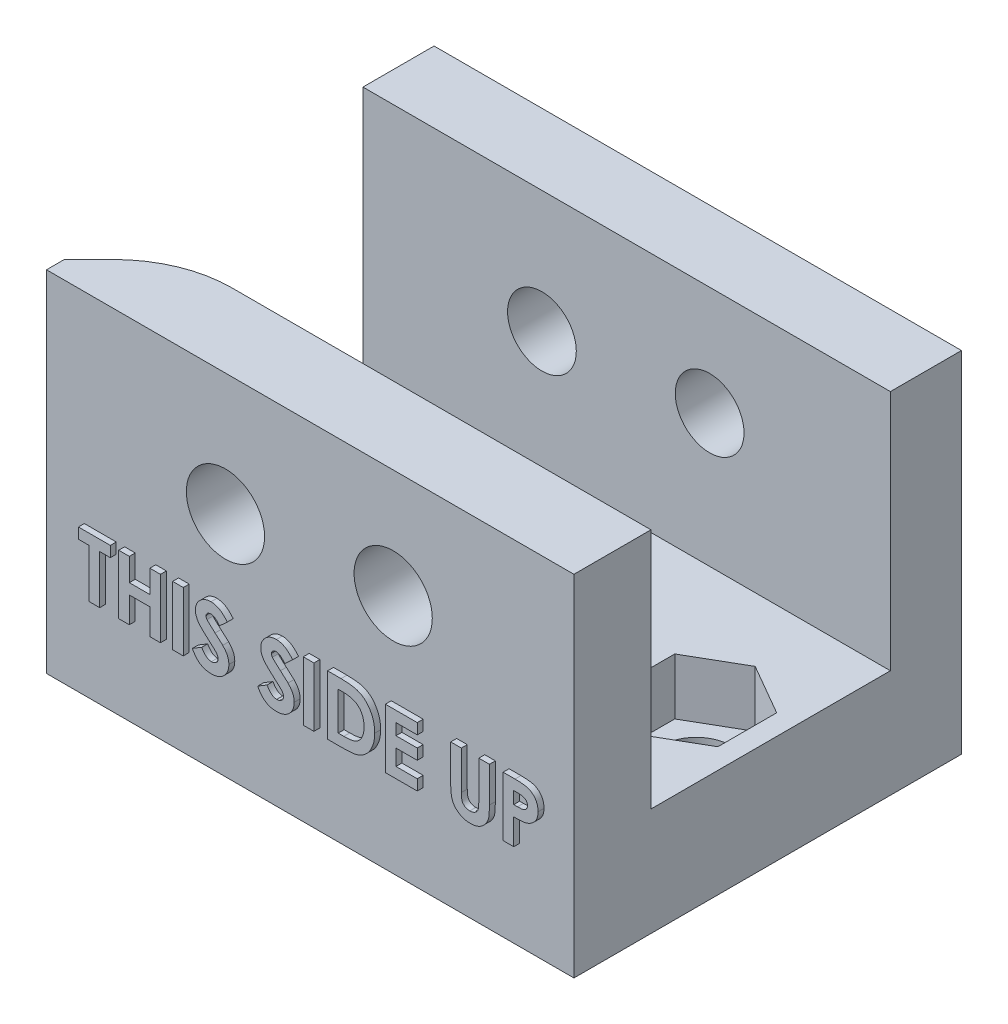
SolidWorks part; units mm, degrees
note: The reader was unsure of these and kept them because the rebuilt part matched: shared geometry of "Sketch2<3>".
material "PETG"
ref_plane "Płaszczyzna przednia" through (0, 0, 0) normal (0, 0, 1) x (1, 0, 0)
ref_plane "Płaszczyzna górna" through (0, 0, 0) normal (0, 1, 0) x (1, 0, 0)
ref_plane "Płaszczyzna prawa" through (0, 0, 0) normal (1, 0, 0) x (0, 0, -1)
sketch "Sketch1" plane through (0, 0, 0) normal (0, 0, 1) x (1, 0, 0)
  line L3 (-14.75, 10) -> (29.75, 10)
  line L4 (-14.75, 10) -> (-14.75, -10)
  line L5 (-14.75, -10) -> (29.75, -10)
  line L6 (29.75, 10) -> (29.75, -10)
  dimension "D5" = 20
extrude "Boss-Extrude1" add sketch "Sketch1" along normal blind 6
sketch "Sketch2" plane through (0, 0, 6) normal (0, 0, 1) x (1, 0, 0)
  line L0 (29.75, -10) -> (29.75, 10) construction
  line L1 (-14.75, -10) -> (29.75, -10)
  line L2 (-14.75, -10) -> (-14.75, -19.5)
  line L3 (-14.75, -19.5) -> (29.75, -19.5)
  line L4 (29.75, -10) -> (29.75, -19.5)
  line L6 (-14.75, -19.5) -> (29.75, -19.5)
  line L7 (-14.75, -19.5) -> (-14.75, -10.4)
  line L8 (-14.75, -10.4) -> (29.75, -10.4)
  line L9 (29.75, -19.5) -> (29.75, -10.4)
  dimension "D1" = 9.5
  dimension "D2" = 9.1
extrude "Boss-Extrude2" add sketch "Sketch2" against normal blind 6
extrude "Boss-Extrude3" add sketch "Sketch2<3>" along normal blind 20.2 contours L8 L2 L3 L4
sketch "Sketch2<3>" plane through (0, 0, 6) normal (0, 0, 1) x (1, 0, 0) same geometry as "Sketch2"
sketch "Sketch3" plane through (0, 0, 26.2) normal (0, 0, 1) x (1, 0, 0)
  line L4 (-14.75, 10) -> (-14.75, -10.4)
  line L5 (-14.75, -10.4) -> (29.75, -10.4)
  line L6 (29.75, -10.4) -> (29.75, 10)
  line L7 (29.75, 10) -> (-14.75, 10)
  line L8 (-14.75, 10) -> (-14.75, -10.4)
  line L10 (29.75, -10.4) -> (29.75, 10)
  line L11 (29.75, 10) -> (-14.75, 10)
  line L12 (29.75, -10.4) -> (-14.75, -10.4)
  line L13 (-14.75, -10.4) -> (-14.75, -19.5)
  line L14 (-14.75, -19.5) -> (29.75, -19.5)
  line L15 (29.75, -19.5) -> (29.75, -10.4)
  line L17 (-14.75, -10.4) -> (-14.75, -19.5)
  line L18 (-14.75, -19.5) -> (29.75, -19.5)
  line L19 (29.75, -19.5) -> (29.75, -10.4)
  dimension "D1" = 0
  dimension "D2" = 0
extrude "Boss-Extrude4" add sketch "Sketch3" along normal blind 6.5
sketch "Sketch4" plane through (0, -19.5, 0) normal (0, -1, 0) x (1, 0, 0)
  line L0 (-14.75, 0) -> (29.75, 0) construction
  line L1 (-2.7, 0) -> (17.7, 0) construction
  line L2 (-2.7, 0) -> (-2.7, 32.7) construction
  line L3 (-2.7, 32.7) -> (17.7, 32.7) construction
  line L4 (17.7, 0) -> (17.7, 32.7) construction
  line L5 (-14.75, 32.7) -> (29.75, 32.7) construction
  line L6 (-2.7, 32.7) -> (-14.75, 32.7) construction
  line L7 (-8.725, 32.7) -> (-8.725, 16.35) construction
  line L8 (-14.75, 0) -> (-14.75, 32.7) construction
  line L9 (-8.725, 16.35) -> (-14.75, 16.35) construction
  line L10 (7.5, 32.7) -> (7.5, 0) construction
  circle A0 centre (-8.725, 16.35) radius 2.9
  circle A1 centre (23.725, 16.35) radius 2.9
  point P8 (7.5, 32.7)
  point P9 (7.5, 32.7)
  dimension "D2" = 5.8
  dimension "D1" = 20.4
extrude "Cut-Extrude1" cut sketch "Sketch4" against normal through all
sketch "Sketch5" plane through (0, -10.4, 0) normal (0, 1, 0) x (1, 0, 0)
  line L1 (-8.725, -11.3848) -> (-13.025, -13.8674)
  line L2 (-13.025, -13.8674) -> (-13.025, -18.8326)
  line L3 (-13.025, -18.8326) -> (-8.725, -21.3152)
  line L4 (-8.725, -21.3152) -> (-4.425, -18.8326)
  line L5 (-4.425, -18.8326) -> (-4.425, -13.8674)
  line L6 (-4.425, -13.8674) -> (-8.725, -11.3848)
  line L7 (23.725, -11.3848) -> (19.425, -13.8674)
  line L8 (19.425, -13.8674) -> (19.425, -18.8326)
  line L9 (19.425, -18.8326) -> (23.725, -21.3152)
  line L10 (23.725, -21.3152) -> (28.025, -18.8326)
  line L11 (28.025, -18.8326) -> (28.025, -13.8674)
  line L12 (28.025, -13.8674) -> (23.725, -11.3848)
  circle A0 centre (-8.725, -16.35) radius 4.3 construction
  circle A1 centre (23.725, -16.35) radius 4.3 construction
  dimension "D1" = 8.6
extrude "Cut-Extrude2" cut sketch "Sketch5" against normal blind 4.75
sketch "Sketch6" plane through (0, -19.5, 0) normal (0, -1, 0) x (1, 0, 0)
  line L0 (-14.75, 0) -> (29.75, 0) construction
  line L1 (-14.75, 32.7) -> (-2.75, 32.7) construction
  line L2 (-14.75, 32.7) -> (-14.75, 0) construction
  line L3 (-14.75, 0) -> (-2.75, 0) construction
  line L4 (-2.75, 32.7) -> (-2.75, 0) construction
  line L5 (-14.75, 32.7) -> (29.75, 32.7) construction
  line L6 (29.75, 0) -> (17.75, 0) construction
  line L7 (29.75, 0) -> (29.75, 32.7) construction
  line L8 (29.75, 32.7) -> (17.75, 32.7) construction
  line L9 (17.75, 0) -> (17.75, 32.7) construction
  line L10 (29.75, 0) -> (29.75, 32.7) construction
  line L11 (-1.75, 31.7) -> (-1.75, 1)
  line L12 (-2.75, 32.7) -> (17.75, 32.7)
  line L13 (-2.75, 32.7) -> (-2.75, 0)
  line L14 (-2.75, 0) -> (17.75, 0)
  line L15 (17.75, 32.7) -> (17.75, 0)
  line L16 (-1.75, 1) -> (16.75, 1)
  line L17 (16.75, 31.7) -> (16.75, 1)
  line L18 (-1.75, 31.7) -> (16.75, 31.7)
  dimension "D1" = 12
  dimension "D2" = 1
extrude "Cut-Extrude3" cut sketch "Sketch6" against normal blind 0.5 contours L18 L11 L16 L17
chamfer "Chamfer1" distance 5 angle 45 1 edges at (-14.75, -0.2, 26.2)
chamfer "Chamfer2" [suppressed] distance 5 angle 45
sketch "Sketch7" [suppressed] plane through (0, 0, 0) normal (0, 0, -1) x (-1, 0, 0)
  text T0 "BOT. RIGHT" font "Century Gothic" height 5.5
sketch "Sketch8" plane through (0, 0, 0) normal (0, 0, -1) x (-1, 0, 0)
  text T0 "BOT. LEFT" font "Century Gothic" height 5.5
extrude "Boss-Extrude5" add sketch "Sketch8" along normal blind 0.5
extrude "Boss-Extrude6" [suppressed] add sketch "Sketch7" along normal blind 0.5
sketch "Sketch9" [suppressed] plane through (0, 0, 32.7) normal (0, 0, 1) x (1, 0, 0)
  text T0 "TOP LEFT" font "Century Gothic" height 5.5
extrude "Boss-Extrude7" [suppressed] add sketch "Sketch9" along normal blind 0.5
sketch "Sketch10" [suppressed] plane through (0, 0, 0) normal (0, 0, -1) x (-1, 0, 0)
  text T0 "THIS SIDE UP" font "Century Gothic" height 5
extrude "Boss-Extrude8" [suppressed] add sketch "Sketch10" along normal blind 0.5
sketch "Sketch11" plane through (0, 0, 32.7) normal (0, 0, 1) x (1, 0, 0)
  text T0 "THIS SIDE UP" font "Century Gothic" height 5
extrude "Boss-Extrude9" add sketch "Sketch11" along normal blind 0.5
hole_wizard "M5 Clearance Hole1" positions "Sketch12" profile "Sketch14" hole size "M5" standard "DIN" end condition up to next
sketch "Sketch12" plane through (0, 0, 0) normal (0, 0, -1) x (-1, 0, 0)
  circle A0 centre (-14.5, 0.8) radius 3 construction
  circle A1 centre (-0.35, -0.3) radius 3 construction
  point P0 (-14.5, 0.8)
  point P2 (-0.35, -0.3)
sketch "Sketch14" plane through (14.5, 0.8, 0) normal (1, 0, 0) x (0, 1, 0)
  line L0 (0, 0) -> (0, 6)
  line L1 (0, 6) -> (2.9, 6)
  line L2 (2.9, 6) -> (2.9, 0)
  line L5 (2.9, 0) -> (0, 0)
  line L11 (0, -6.35) -> (0, 107.95) construction
  dimension "Thru Hole Dia." = 5.8
  dimension "Thru Hole Depth" = 6
sketch "Sketch15" plane through (0, 0, 32.7) normal (0, 0, 1) x (1, 0, 0)
  circle A0 centre (0.35, -0.3) radius 3.3
  circle A1 centre (14.5, 0.8) radius 3.3
  circle A2 centre (0.35, -0.3) radius 2.9 construction
  circle A3 centre (14.5, 0.8) radius 2.9 construction
  dimension "D1" = 6.6
extrude "Cut-Extrude4" cut sketch "Sketch15" against normal up to next and the other way through all
hole_wizard "M5 Clearance Hole2" [suppressed] positions "Sketch16" profile "Sketch17" hole size "M5" standard "DIN"
sketch "Sketch16" plane through (0, 0, 0) normal (0, 0, -1) x (-1, 0, 0)
  circle A0 centre (-13.65, -0.1) radius 3 construction
  circle A1 centre (1.35, -0.4) radius 3 construction
  point P0 (-13.65, -0.1)
  point P2 (1.35, -0.4)
sketch "Sketch17" plane through (13.65, -0.1, 0) normal (1, 0, 0) x (0, 1, 0)
  line L0 (0, 0) -> (0, 6)
  line L1 (0, 6) -> (2.9, 6)
  line L2 (2.9, 6) -> (2.9, 0)
  line L5 (2.9, 0) -> (0, 0)
  line L11 (0, -6.35) -> (0, 107.95) construction
  dimension "Thru Hole Dia." = 5.8
  dimension "Thru Hole Depth" = 6
hole_wizard "Ø6.6 (6.6) Diameter Hole1" [suppressed] positions "Sketch18" profile "Sketch19" hole size "Ø6.6" standard "DIN"
sketch "Sketch18" plane through (0, 0, 32.7) normal (0, 0, 1) x (1, 0, 0)
  circle A0 centre (-1.35, -0.4) radius 2.9 construction
  circle A1 centre (13.65, -0.1) radius 2.9 construction
  point P0 (-1.35, -0.4)
  point P2 (13.65, -0.1)
sketch "Sketch19" plane through (-1.35, -0.4, 32.7) normal (1, 0, 0) x (0, -1, 0)
  line L0 (0, 0) -> (0, 6.5)
  line L1 (0, 6.5) -> (3.3, 6.5)
  line L2 (3.3, 6.5) -> (3.3, 0)
  line L5 (3.3, 0) -> (0, 0)
  line L11 (0, -6.35) -> (0, 107.95) construction
  dimension "Thru Hole Dia." = 6.6
  dimension "Thru Hole Depth" = 6.5
fillet "Fillet1" radius 10 1 edges at (-9.75, -0.2, 26.2)
fillet "Fillet2" [suppressed] radius 10
hole_wizard "M5 Clearance Hole3" [suppressed] positions "Sketch20" profile "Sketch21" hole size "M5" standard "DIN"
sketch "Sketch20" plane through (0, 0, 0) normal (0, 0, -1) x (-1, 0, 0)
  circle A0 centre (-28.6151, 9.2961) radius 3 construction
  circle A2 centre (-13.4651, 9.2961) radius 3 construction
  point P0 (-28.6151, 9.2961)
  point P2 (-13.4651, 9.2961)
sketch "Sketch21" plane through (28.6151, 9.2961, 0) normal (1, 0, 0) x (0, 1, 0)
  line L0 (0, 0) -> (0, 6)
  line L1 (0, 6) -> (2.9, 6)
  line L2 (2.9, 6) -> (2.9, 0)
  line L5 (2.9, 0) -> (0, 0)
  line L11 (0, -6.35) -> (0, 107.95) construction
  dimension "Thru Hole Dia." = 5.8
  dimension "Thru Hole Depth" = 6
hole_wizard "Ø6.6 (6.6) Diameter Hole2" [suppressed] positions "Sketch22" profile "Sketch23" hole size "Ø6.6" standard "DIN"
sketch "Sketch22" plane through (0, 0, 32.7) normal (0, 0, 1) x (1, 0, 0)
  circle A0 centre (28.6151, 9.2961) radius 2.9 construction
  circle A1 centre (13.4651, 9.2961) radius 2.9 construction
  point P0 (28.6151, 9.2961)
  point P2 (13.4651, 9.2961)
sketch "Sketch23" plane through (28.6151, 9.2961, 32.7) normal (1, 0, 0) x (0, -1, 0)
  line L0 (0, 0) -> (0, 6.5)
  line L1 (0, 6.5) -> (3.3, 6.5)
  line L2 (3.3, 6.5) -> (3.3, 0)
  line L5 (3.3, 0) -> (0, 0)
  line L11 (0, -6.35) -> (0, 107.95) construction
  dimension "Thru Hole Dia." = 6.6
  dimension "Thru Hole Depth" = 6.5
sketch "Sketch24" [suppressed] plane through (0, 0, 32.7) normal (0, 0, 1) x (1, 0, 0)
  text T0 "TOP RIGHT" font "Century Gothic" height 5.5
extrude "Boss-Extrude10" [suppressed] add sketch "Sketch24" along normal blind 0.5
hole_wizard "M5 Clearance Hole4" [suppressed] positions "Sketch25" profile "Sketch26" hole size "M5" standard "DIN"
sketch "Sketch25" plane through (0, 0, 0) normal (0, 0, -1) x (-1, 0, 0)
  circle A0 centre (-16.9, -0.35) radius 3 construction
  circle A1 centre (-0.6, -0.35) radius 3 construction
  point P0 (-16.9, -0.35)
  point P2 (-0.6, -0.35)
sketch "Sketch26" plane through (16.9, -0.35, 0) normal (1, 0, 0) x (0, 1, 0)
  line L0 (0, 0) -> (0, 6)
  line L1 (0, 6) -> (2.9, 6)
  line L2 (2.9, 6) -> (2.9, 0)
  line L5 (2.9, 0) -> (0, 0)
  line L11 (0, -6.35) -> (0, 107.95) construction
  dimension "Thru Hole Dia." = 5.8
  dimension "Thru Hole Depth" = 6
hole_wizard "Ø6.6 (6.6) Diameter Hole3" [suppressed] positions "Sketch27" profile "Sketch28" hole size "Ø6.6" standard "DIN"
sketch "Sketch27" plane through (0, 0, 32.7) normal (0, 0, 1) x (1, 0, 0)
  circle A0 centre (0.6, -0.35) radius 2.9 construction
  circle A1 centre (16.9, -0.35) radius 2.9 construction
  point P0 (0.6, -0.35)
  point P2 (16.9, -0.35)
sketch "Sketch28" plane through (0.6, -0.35, 32.7) normal (1, 0, 0) x (0, -1, 0)
  line L0 (0, 0) -> (0, 6.5)
  line L1 (0, 6.5) -> (3.3, 6.5)
  line L2 (3.3, 6.5) -> (3.3, 0)
  line L5 (3.3, 0) -> (0, 0)
  line L11 (0, -6.35) -> (0, 107.95) construction
  dimension "Thru Hole Dia." = 6.6
  dimension "Thru Hole Depth" = 6.5
equation "\"D1@Sketch2\"=\"D2@Sketch2\"+0.4"
